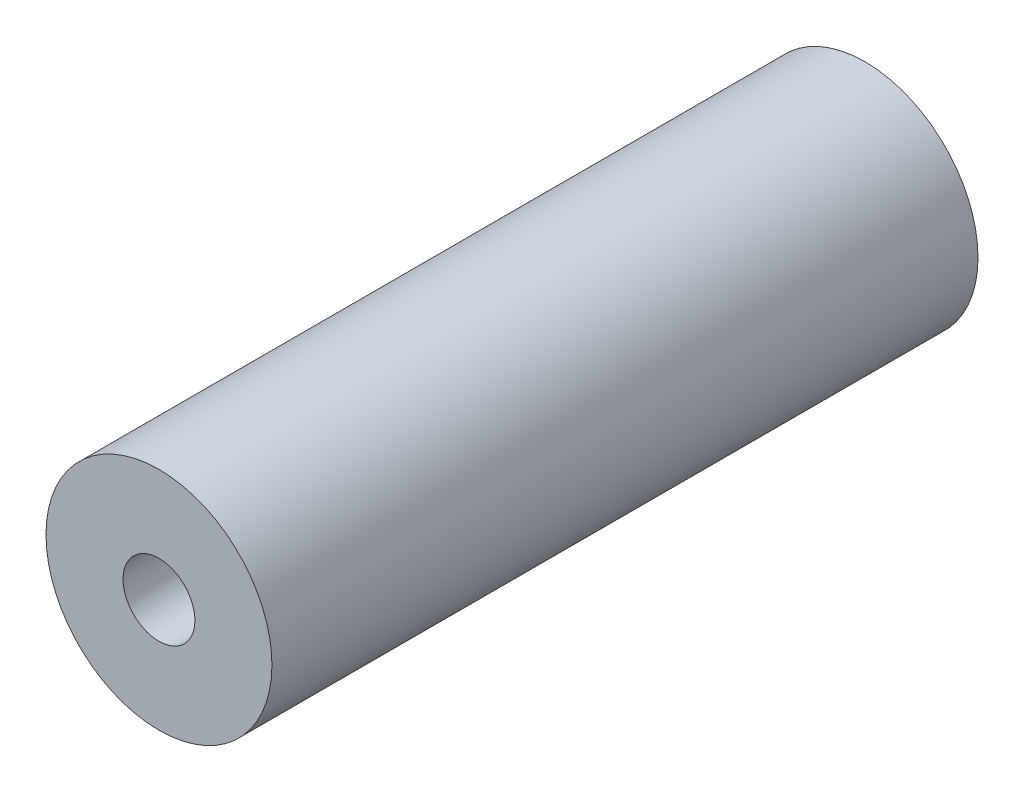
SolidWorks part; units mm, degrees
ref_plane "Front Plane" through (0, 0, 0) normal (0, 0, 1) x (1, 0, 0)
ref_plane "Top Plane" through (0, 0, 0) normal (0, 1, 0) x (1, 0, 0)
ref_plane "Right Plane" through (0, 0, 0) normal (1, 0, 0) x (0, 0, -1)
sketch "Sketch1" plane through (0, 0, 0) normal (0, 0, 1) x (1, 0, 0)
  circle A1 centre (0, 0) radius 6.35
  circle A2 centre (0, 0) radius 2.0193
  dimension "D2" = 12.7
  dimension "D3" = 4.0386
extrude "Boss-Extrude1" add sketch "Sketch1" along normal mid plane 39.6875 contours A1 A2 region at (-6.1704, 0, 0)
